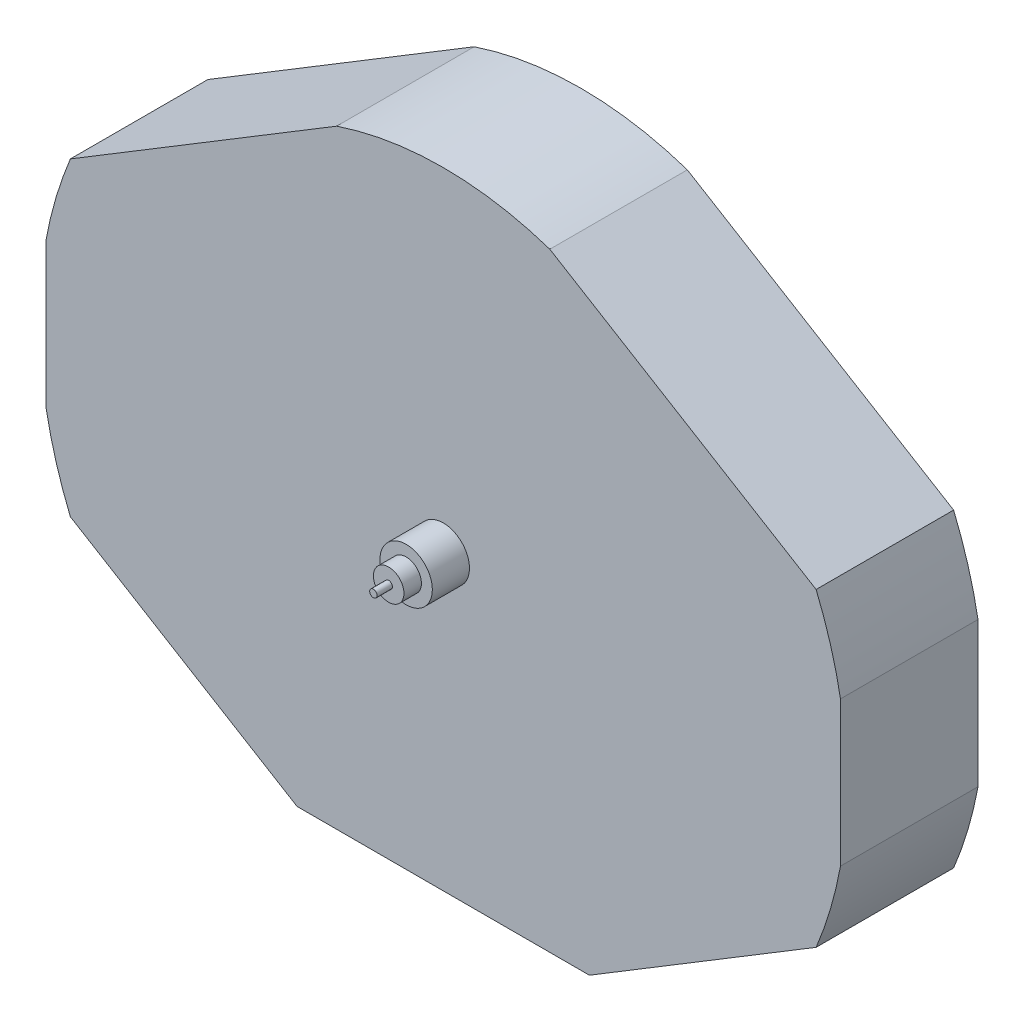
SolidWorks part; units mm, degrees
ref_plane "Plan de face" through (0, 0, 0) normal (0, 0, 1) x (1, 0, 0)
ref_plane "Plan de dessus" through (0, 0, 0) normal (0, 1, 0) x (1, 0, 0)
ref_plane "Plan de droite" through (0, 0, 0) normal (1, 0, 0) x (0, 0, -1)
sketch "Esquisse2" plane through (0, 0, 0) normal (0, 0, 1) x (1, 0, 0)
  line L0 (9.1, 1.6591) -> (9.1, -1.6591)
  line L1 (0, 0) -> (0, 7.65) construction
  line L2 (0, 0) -> (12.4009, 0) construction
  line L3 (2.4413, 7.25) -> (8.5417, 3.55)
  line L4 (-9.1, 1.6591) -> (-9.1, -1.6591)
  line L5 (-2.4413, 7.25) -> (-8.5417, 3.55)
  line L6 (-3.3481, -6.7) -> (3.3481, -6.7)
  line L8 (0, 0) -> (0, -6.7) construction
  line L10 (-3.3481, -6.7) -> (-8.5417, -3.55)
  line L11 (3.3481, -6.7) -> (8.5417, -3.55)
  arc A0 (2.4413, 7.25) -> (-2.4413, 7.25) centre (0, 0) ccw
  arc A1 (9.1, 1.6591) -> (8.5417, 3.55) centre (0, 0) ccw
  arc A2 (-9.1, 1.6591) -> (-8.5417, 3.55) centre (0, 0) cw
  arc A6 (-9.1, -1.6591) -> (-8.5417, -3.55) centre (0, 0) ccw
  arc A7 (9.1, -1.6591) -> (8.5417, -3.55) centre (0, 0) cw
  point P1 (-9.1, 0)
  point P6 (2.4413, 7.25)
  point P8 (8.5417, 3.55)
  point P11 (-2.4413, -7.25)
  point P14 (-8.5417, 3.55)
  point P15 (-2.4413, 7.25)
  point P22 (9.1, 0)
  point P23 (-8.5417, -3.55)
  point P24 (8.5417, -3.55)
  point P25 (2.4413, -7.25)
  dimension "D1" = 15.3
  dimension "D4" = 9.25
  dimension "D2" = 18.2
  dimension "D3" = 7.1
  dimension "D5" = 7.25
  dimension "D6" = 6.7
  dimension "D7" = 31.238
extrude "Boss.-Extru.1" add sketch "Esquisse2" along normal blind 3.15
sketch "Esquisse3" plane through (0, 0, 3.15) normal (0, 0, 1) x (1, 0, 0)
  line L0 (0, 7.65) -> (0, 0) construction
  line L1 (0, 0) -> (9.1, 0) construction
  line L2 (9.1, -1.6591) -> (9.1, 1.6591) construction
  arc A0 (2.4413, 7.25) -> (-2.4413, 7.25) centre (0, 0) ccw construction
  point P0 (-7.9, -3)
  point P1 (8.234, -1.9)
  dimension "D1" = 1.9
  dimension "D2" = 8.234
  dimension "D3" = 3
  dimension "D4" = 7.9
ref_axis "DH1" through (-7.9, -3, 3.15) along (0, 0, 1)
ref_axis "DH2" through (8.234, -1.9, 3.15) along (0, 0, 1)
sketch "Esquisse4" plane through (0, 0, 3.15) normal (0, 0, 1) x (1, 0, 0)
  circle A0 centre (0, 0) radius 0.6
  dimension "D1" = 1.2
extrude "Boss.-Extru.2" add sketch "Esquisse4" along normal blind 0.85
sketch "Esquisse5" plane through (0, 0, 4) normal (0, 0, 1) x (1, 0, 0)
  circle A0 centre (0, 0) radius 0.35
  dimension "D1" = 0.7
extrude "Boss.-Extru.3" add sketch "Esquisse5" along normal blind 0.4
sketch "Esquisse6" plane through (0, 0, 4.4) normal (0, 0, 1) x (1, 0, 0)
  circle A0 centre (0, 0) radius 0.085
  dimension "D1" = 0.17
extrude "Boss.-Extru.4" add sketch "Esquisse6" along normal blind 0.35
